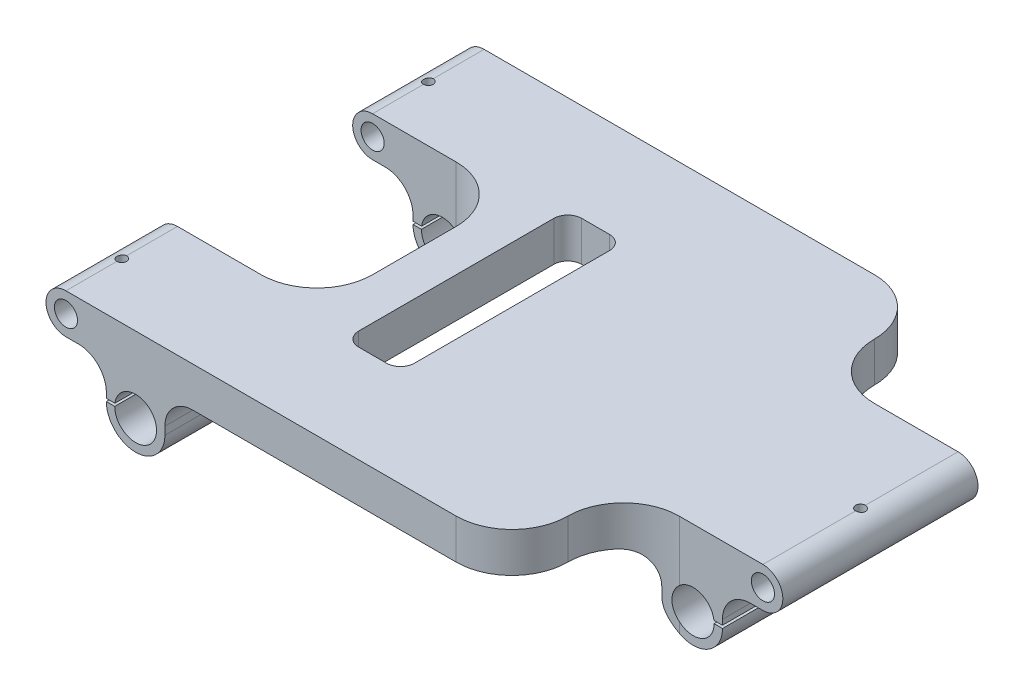
SolidWorks part; units mm, degrees
ref_plane "Front Plane" through (0, 0, 0) normal (0, 0, 1) x (1, 0, 0)
ref_plane "Top Plane" through (0, 0, 0) normal (0, 1, 0) x (1, 0, 0)
ref_plane "Right Plane" through (0, 0, 0) normal (1, 0, 0) x (0, 0, -1)
sketch "Sketch5" plane through (0, 0, 0) normal (0, 0, 1) x (1, 0, 0)
  line L0 (-80, 0) -> (0, 0) construction
  line L1 (0, 0) -> (80, 0) construction
  line L2 (-90.5, 0) -> (-90.5, 12.85)
  line L3 (-90.5, 12.85) -> (-105, 12.85)
  line L5 (0, 0) -> (0, 20) construction
  line L6 (-105, 27.15) -> (105, 27.15)
  line L7 (90.5, 12.85) -> (105, 12.85)
  line L8 (90.5, 0) -> (90.5, 12.85)
  line L9 (-69.5, 0) -> (69.5, 0)
  circle A0 centre (-80, 0) radius 7.5
  circle A1 centre (80, 0) radius 7.5
  circle A2 centre (-105, 20) radius 4.15
  circle A3 centre (105, 20) radius 4.15
  arc A4 (-90.5, 0) -> (-80, -10.5) centre (-80, 0) ccw
  arc A5 (-105, 27.15) -> (-105, 12.85) centre (-105, 20) ccw
  arc A6 (105, 27.15) -> (105, 12.85) centre (105, 20) cw
  arc A7 (90.5, 0) -> (80, -10.5) centre (80, 0) cw
  arc A8 (80, -10.5) -> (69.5, 0) centre (80, 0) cw
  arc A9 (-80, -10.5) -> (-69.5, 0) centre (-80, 0) ccw
  point P11 (0, 27.15)
  point P23 (0, -10.5)
  dimension "D2" = 15
  dimension "D3" = 8.3
  dimension "D6" = 8.3
  dimension "D9" = 3
  dimension "D10" = 3
  dimension "D1" = 80
  dimension "D7" = 20
  dimension "D8" = 105
extrude "Boss-Extrude4" add sketch "Sketch5" along normal blind 150
sketch "Sketch7" plane through (0, 27.15, 0) normal (0, 1, 0) x (1, 0, 0)
  line L0 (105, -150) -> (-105, -150) construction
  line L1 (-55, -110) -> (-144.175, -110)
  line L2 (-55, -110) -> (-55, -40)
  line L3 (-55, -40) -> (-144.175, -40)
  line L4 (-144.175, -110) -> (-144.175, -40)
  line L5 (105, 0) -> (-105, 0) construction
  line L6 (-105, -150) -> (-105, 0) construction
  line L8 (105, -150) -> (105, 0) construction
  line L9 (179.0512, -169.1017) -> (55, -169.1017)
  line L10 (179.0512, -169.1017) -> (179.0512, -110)
  line L11 (179.0512, -110) -> (55, -110)
  line L12 (55, -169.1017) -> (55, -110)
  line L13 (147.105, -40) -> (55, -40)
  line L14 (147.105, -40) -> (147.105, 29.543)
  line L15 (147.105, 29.543) -> (55, 29.543)
  line L16 (55, -40) -> (55, 29.543)
  dimension "D1" = 40
  dimension "D2" = 40
  dimension "D3" = 50
  dimension "D4" = 50
extrude "Cut-Extrude3" cut sketch "Sketch7" against normal blind 150
fillet "Fillet2" radius 20 2 edges at (55, 13.575, 0) (55, 13.575, 150)
fillet "Fillet3" radius 20 2 edges at (55, 13.575, 40) (55, 13.575, 110)
fillet "Fillet4" radius 20 2 edges at (-55, 13.575, 40) (-55, 13.575, 110)
sketch "Sketch8" plane through (0, 0, 0) normal (0, -1, 0) x (1, 0, 0)
  line L2 (-45, 150) -> (-69.5, 150)
  line L10 (-69.5, 0) -> (35, 0)
  line L11 (69.5, 39.2289) -> (69.5, 110.7711)
  line L12 (35, 150) -> (-69.5, 150)
  line L13 (-69.5, 150) -> (-69.5, 109.2289)
  line L14 (-55, 90) -> (-55, 60)
  line L15 (-69.5, 40.7711) -> (-69.5, 0)
  line L20 (-59.5, 0) -> (35, 0)
  line L21 (69.5, 39.2289) -> (69.5, 110.7711)
  line L22 (35, 150) -> (-59.5, 150)
  line L23 (-69.5, 150) -> (-69.5, 109.2289)
  line L24 (-55, 90) -> (-55, 60)
  line L25 (-69.5, 40.7711) -> (-69.5, 0)
  arc A6 (35, 0) -> (55, 20) centre (35, 20) ccw
  arc A7 (69.5, 39.2289) -> (55, 20) centre (75, 20) ccw
  arc A8 (55, 130) -> (69.5, 110.7711) centre (75, 130) ccw
  arc A9 (55, 130) -> (35, 150) centre (35, 130) ccw
  arc A10 (-55, 90) -> (-69.5, 109.2289) centre (-75, 90) ccw
  arc A11 (-69.5, 40.7711) -> (-55, 60) centre (-75, 60) ccw
  arc A12 (35, 0) -> (55, 20) centre (35, 20) ccw
  arc A13 (69.5, 39.2289) -> (55, 20) centre (75, 20) ccw
  arc A14 (55, 130) -> (69.5, 110.7711) centre (75, 130) ccw
  arc A15 (55, 130) -> (35, 150) centre (35, 130) ccw
  arc A16 (-55, 90) -> (-69.5, 109.2289) centre (-75, 90) ccw
  arc A17 (-69.5, 40.7711) -> (-55, 60) centre (-75, 60) ccw
  line M19 (-69.5, 0) -> (35, 0)
  arc M20 (35, 0) -> (55, 20) centre (35, 20) ccw
  arc M21 (55, 20) -> (69.5, 39.2289) centre (75, 20) cw
  line M22 (69.5, 39.2289) -> (69.5, 110.7711)
  arc M23 (69.5, 110.7711) -> (55, 130) centre (75, 130) cw
  arc M24 (55, 130) -> (35, 150) centre (35, 130) ccw
  line M25 (35, 150) -> (-69.5, 150)
  line M26 (-69.5, 150) -> (-69.5, 109.2289)
  arc M27 (-69.5, 109.2289) -> (-55, 90) centre (-75, 90) cw
  line M28 (-55, 90) -> (-55, 60)
  arc M29 (-55, 60) -> (-69.5, 40.7711) centre (-75, 60) cw
  line M30 (-69.5, 40.7711) -> (-69.5, 0)
  line M31 (-69.5, 0) -> (35, 0)
  dimension "D1" = 0
extrude "Cut-Extrude4" cut sketch "Sketch8" against normal up to surface (12.85 mm away) contours M19 M20 M21 M22 M23 M24 M25 | M31 M25 M26 M27 M28 M29 M30 region at (-0.9395, 0, 75) up to face at (97.75, 12.85, 75)
ref_plane "Plane3" through (0, 0, 75) normal (0, 0, -1) x (-1, 0, 0)
fillet "Fillet6" radius 10 6 edges at (90.5, 12.85, 75) (69.5, 12.85, 75) (-90.5, 12.85, 20) (-90.5, 12.85, 130) (-69.5, 12.85, 20.3856) (-69.5, 12.85, 129.6144)
sketch "Sketch12" plane through (0, 27.15, 0) normal (0, 1, 0) x (1, 0, 0)
  line L0 (-105, -40) -> (-105, 0) construction
  line L1 (-105, -150) -> (-105, -110) construction
  line L2 (105, -110) -> (105, -40) construction
  circle A0 centre (-105, -20) radius 1.75
  circle A1 centre (-105, -130) radius 1.75
  circle A2 centre (105, -75) radius 1.75
  dimension "D1" = 3.5
extrude "Cut-Extrude8" cut sketch "Sketch12" against normal blind 208
sketch "Sketch13" plane through (0, 12.85, 0) normal (0, -1, 0) x (-1, 0, 0)
  line L1 (25, -35) -> (35, -35)
  line L2 (20, -40) -> (20, -110)
  line L3 (25, -115) -> (35, -115)
  line L4 (40, -40) -> (40, -110)
  line L5 (55, -90) -> (55, -60) construction
  arc A0 (20, -110) -> (25, -115) centre (25, -110) ccw
  arc A1 (35, -115) -> (40, -110) centre (35, -110) ccw
  arc A2 (35, -35) -> (40, -40) centre (35, -40) cw
  arc A3 (25, -35) -> (20, -40) centre (25, -40) ccw
  point P4 (30, -115)
  point P5 (40, -75)
  point P9 (55, -75)
  point P12 (20, -115)
  point P17 (40, -35)
  point P20 (20, -35)
  dimension "D5" = 5
  dimension "D1" = 20
  dimension "D2" = 65
  dimension "D3" = 80
  dimension "D4" = 0
extrude "Cut-Extrude9" cut sketch "Sketch13" against normal blind 20
sketch "Sketch15" plane through (-90.5, 0, 0) normal (-1, 0, 0) x (0, 0, 1)
  line L0 (150, 0) -> (0, 0)
extrude "Cut-Extrude-Thin1" cut sketch "Sketch15" against normal blind 10 thin thin type one direction wall 1
sketch "Sketch16" plane through (90.5, 0, 0) normal (1, 0, 0) x (0, 0, -1)
  line L0 (-40, 0) -> (-110, 0)
extrude "Cut-Extrude-Thin2" cut sketch "Sketch16" against normal blind 10 thin thin type one direction wall 1
